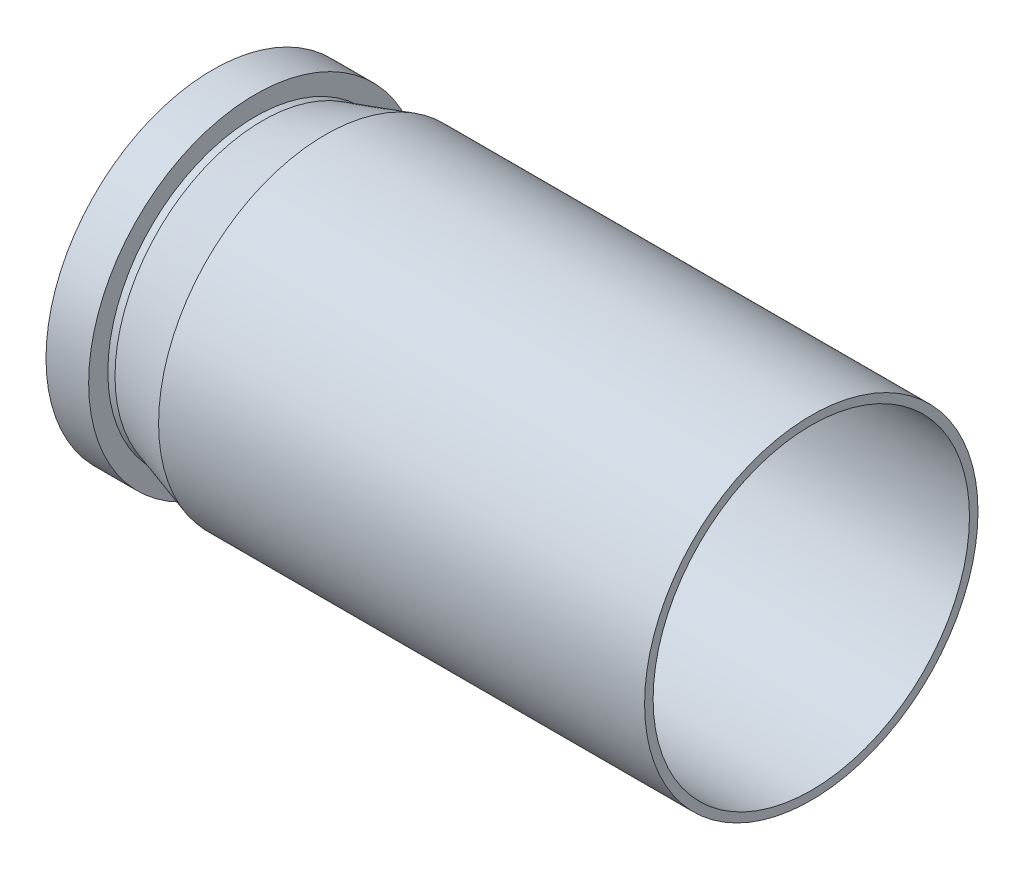
SolidWorks part; units mm, degrees
ref_plane "Plano frontal" through (0, 0, 0) normal (0, 0, 1) x (1, 0, 0)
ref_plane "Plano superior" through (0, 0, 0) normal (0, 1, 0) x (1, 0, 0)
ref_plane "Plano direito" through (0, 0, 0) normal (1, 0, 0) x (0, 0, -1)
sketch "Esboço1" plane through (0, 0, 0) normal (0, 0, 1) x (1, 0, 0)
  line L0 (4.16, 1) -> (4.16, 4.45)
  line L1 (4.16, 4.45) -> (16.84, 4.45)
  line L2 (16.84, 4.45) -> (16.84, 4.69)
  line L3 (16.84, 4.69) -> (3.2, 4.69)
  line L4 (3.2, 4.69) -> (3.2, 4.15)
  line L5 (3.2, 4.15) -> (1.2, 4.15)
  line L6 (1.2, 4.15) -> (1.2, 4.69)
  line L7 (1.2, 4.69) -> (0, 4.69)
  line L8 (0, 4.69) -> (0, 2.25)
  line L9 (0, 2.25) -> (3, 2.25)
  line L10 (3, 2.25) -> (3, 1)
  line L11 (3, 1) -> (4.16, 1)
  line L12 (0, 0) -> (22.3463, 0) construction
  dimension "D1" = 1.2
  dimension "D2" = 2
  dimension "D4" = 0.24
  dimension "D5" = 0.54
  dimension "D6" = 3.69
  dimension "D7" = 3
  dimension "D8" = 4.16
  dimension "D9" = 2.44
  dimension "D10" = 4.69
  dimension "D11" = 12.68
  dimension "D12" = 1
revolve "Revolução1" add sketch "Esboço1" angle 360 about L12
chamfer "Chanfro4" distance 0.55 angle 73 1 edges at (3.2, 0, 4.15) first distance on face at (3.2, 0, 4.15)
